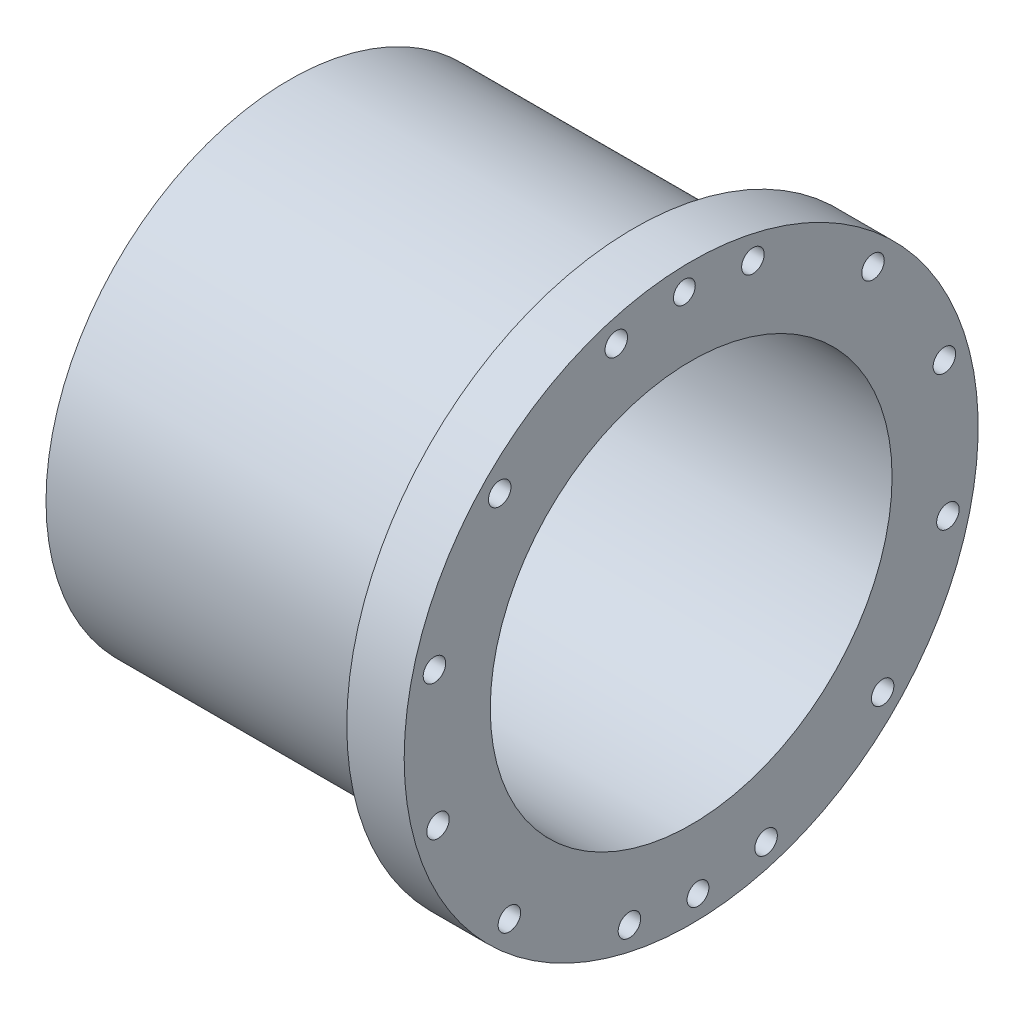
SolidWorks part; units mm, degrees
material "6061-T6 (SS)"
ref_plane "Front Plane" through (0, 0, 0) normal (0, 0, 1) x (1, 0, 0)
ref_plane "Top Plane" through (0, 0, 0) normal (0, 1, 0) x (1, 0, 0)
ref_plane "Right Plane" through (0, 0, 0) normal (1, 0, 0) x (0, 0, -1)
sketch "Sketch1" plane through (0, 0, 0) normal (0, 0, 1) x (1, 0, 0)
  line L0 (-87.2836, 0) -> (119.6109, 0) construction
  line L1 (-88.9, 53.848) -> (-88.9, 44.45)
  line L2 (-88.9, 44.45) -> (0, 44.45)
  line L3 (0, 44.45) -> (0, 63.5)
  line L4 (0, 63.5) -> (-12.7, 63.5)
  line L5 (-12.7, 63.5) -> (-12.7, 53.848)
  line L6 (-12.7, 53.848) -> (-88.9, 53.848)
  dimension "D1" = 88.9
  dimension "D2" = 88.9
  dimension "D3" = 19.05
  dimension "D4" = 9.398
  dimension "D5" = 12.7
revolve "Revolve1" add sketch "Sketch1" angle 360 about L0
ref_axis "Axis1" through (4.445, 0, 0) along (-1, 0, 0)
ref_plane "Plane1" through (0, 0, 0) normal (0, 0.7071, 0.7071) x (-1, 0, 0)
ref_plane "Plane2" through (0, 0, 0) normal (0, -0.7071, 0.7071) x (-1, 0, 0)
sketch "Sketch7" plane through (0, 0, 0) normal (1, 0, 0) x (0, 0, -1)
  circle A0 centre (-16.5715, 56.0204) radius 2.4892
  circle A1 centre (13.6589, 56.8008) radius 2.4892
  circle A2 centre (40.2293, 42.3615) radius 2.4892
  circle A3 centre (56.0204, 16.5715) radius 2.4892
  circle A4 centre (56.8008, -13.6589) radius 2.4892
  circle A5 centre (42.3615, -40.2293) radius 2.4892
  circle A6 centre (16.5715, -56.0204) radius 2.4892
  circle A7 centre (-13.6589, -56.8008) radius 2.4892
  circle A8 centre (-40.2293, -42.3615) radius 2.4892
  circle A9 centre (-56.0204, -16.5715) radius 2.4892
  circle A10 centre (-56.8008, 13.6589) radius 2.4892
  circle A11 centre (-42.3615, 40.2293) radius 2.4892
  circle A12 centre (0, 0) radius 58.42 construction
  dimension "D2" = 4.9784
  dimension "D1" = 12
extrude "Cut-Extrude1" cut sketch "Sketch7" against normal through all
sketch "Sketch8" plane through (-88.9, 0, 0) normal (-1, 0, 0) x (0, 0, 1)
  line L0 (-40.2293, 42.3615) -> (40.2293, -42.3615) construction
  circle A0 centre (0, 0) radius 49.149 construction
  dimension "D1" = 98.298
hole_wizard "#21 (0.159) Diameter Hole1" positions "Sketch12" profile "Sketch13" hole size "#21" standard "ANSI Inch"
sketch "Sketch12" plane through (-88.9, 0, 0) normal (-1, 0, 0) x (0, 0, 1)
  line L0 (-40.2293, 42.3615) -> (40.2293, -42.3615) construction
  circle A0 centre (0, 0) radius 49.149 construction
  point P0 (-33.8451, 35.6389)
  point P10 (1.2684, 49.1326)
  point P11 (35.6389, 33.8451)
  point P12 (49.1326, -1.2684)
  point P13 (33.8451, -35.6389)
  point P14 (-1.2684, -49.1326)
  point P15 (-35.6389, -33.8451)
  point P16 (-49.1326, 1.2684)
  dimension "D1" = 8
sketch "Sketch13" plane through (-88.9, 35.6389, -33.8451) normal (0, 1, 0) x (0, 0, 1)
  line L0 (0, 0) -> (0, 18.9933)
  line L1 (0, 18.9933) -> (2.0193, 17.78)
  line L2 (2.0193, 17.78) -> (2.0193, 0)
  line L5 (2.0193, 0) -> (0, 0)
  line L10 (0, 18.9933) -> (-2.0193, 17.78) construction
  line L11 (0, -6.35) -> (0, 107.95) construction
  dimension "Hole Dia." = 4.0386
  dimension "Hole Depth" = 17.78
  dimension "Drill Angle" = 118
sketch "Sketch15" plane through (0, 0, 0) normal (1, 0, 0) x (0, 0, -1)
  line L0 (-16.5715, 56.0204) -> (13.6589, 56.8008) construction
  line L1 (0, 0) -> (-1.8888, 73.1633) construction
  line L2 (0, 0) -> (1.8455, -71.4871) construction
  line L3 (-13.6589, -56.8008) -> (16.5715, -56.0204) construction
  circle A0 centre (0, 0) radius 58.42 construction
  circle A1 centre (-1.5077, 58.4005) radius 2.413
  circle A2 centre (1.5077, -58.4005) radius 2.413
  dimension "D1" = 4.826
extrude "Cut-Extrude2" cut sketch "Sketch15" against normal blind 4.826
